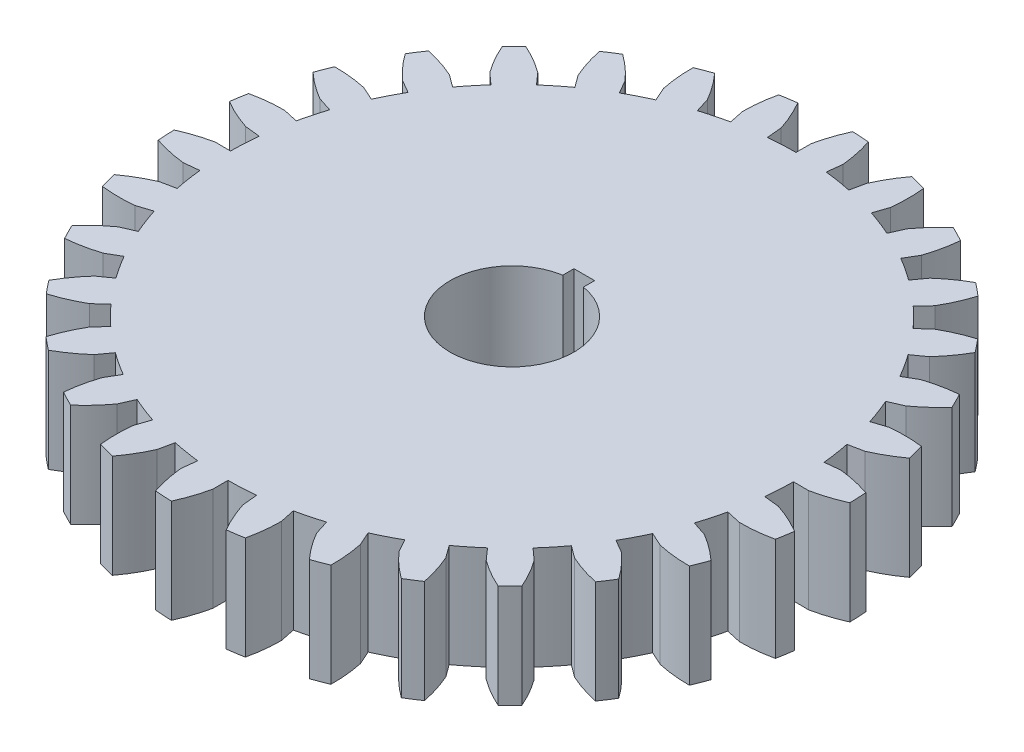
SolidWorks part; units mm, degrees
ref_plane "Front Plane" through (0, 0, 0) normal (0, 0, 1) x (1, 0, 0)
ref_plane "Top Plane" through (0, 0, 0) normal (0, 1, 0) x (1, 0, 0)
ref_plane "Right Plane" through (0, 0, 0) normal (1, 0, 0) x (0, 0, -1)
sketch "Sketch1" plane through (0, 0, 0) normal (0, 1, 0) x (1, 0, 0)
  circle A3 centre (0, 0) radius 13.75
  circle A4 centre (0, 0) radius 16
  circle A5 centre (0, 0) radius 15
  circle A6 centre (0, 0) radius 14
  circle A7 centre (0, 0) radius 14.4889
  dimension "pitch circle" = 30
  dimension "addendum circle" = 32
  dimension "root circle" = 27.5
  dimension "clearance circle" = 28
  dimension "base circle" = 28.9778
sketch "Sketch2" plane through (0, 0, 0) normal (0, 1, 0) x (1, 0, 0)
  line L0 (0, 0) -> (0, 14.4889)
  line L1 (0, 0) -> (7.2444, 12.5477) construction
  line L2 (0, 0) -> (12.5477, 7.2444) construction
  line L3 (0, 0) -> (14.4889, 0) construction
  line L4 (14.4889, 0) -> (14.4889, 22.7591) construction
  line L5 (12.5477, 7.2444) -> (4.9614, 20.3844) construction
  line L6 (7.2444, 12.5477) -> (0.6745, 16.3409) construction
  line L7 (0, 0) -> (3.1187, 14.6722)
  line L8 (0, 0) -> (1.5679, 14.9178) construction
  line L9 (0.8496, 14.9759) -> (0, 0) construction
  circle A0 centre (0, 0) radius 14.4889 construction
  circle A1 centre (0, 0) radius 15 construction
  arc A2 (1.5679, 14.9178) -> (0.1294, 14.9994) centre (0, 0) ccw
  spline S0 degree 3 poles (0, 14.4889) (1.2745, 20.4223) (9.5995, 22.7668) (14.4889, 22.7591) knots 0 0 0 0 1 1 1 1
  spline S1 degree 3 poles (1.6388, 14.3959) (1.0435, 20.4354) (-6.9629, 23.7065) (-11.8218, 24.2518) knots 0 0 0 0 1 1 1 1
  point P11 (0, 0)
  dimension "Involute Control" = 90
  dimension "Base circle quarter circumference" = 22.7591
  dimension "D1" = 15.1727
  dimension "D2" = 7.5864
  dimension "pitch circle" = 12
  dimension "Involute array" = 4
sketch "Sketch3" plane through (0, 0, 0) normal (0, 1, 0) x (1, 0, 0)
  line L0 (1.6388, 14.3959) -> (1.5552, 13.6618)
  line L1 (0, 0) -> (0, 14.4889) construction
  line L3 (0, 13.75) -> (0, 14.4889)
  arc A1 (0.502, 15.9921) -> (0, 14.4889) centre (7.0112, 12.9829) ccw
  circle A2 centre (0, 0) radius 16 construction
  circle A3 centre (0, 0) radius 13.75 construction
  arc A7 (1.6388, 14.3959) -> (1.31, 15.9463) centre (-5.4978, 13.6925) ccw
  arc A8 (1.5552, 13.6618) -> (0, 13.75) centre (0, 0) ccw
  arc A9 (1.31, 15.9463) -> (0.502, 15.9921) centre (0, 0) ccw
  circle A10 centre (0, 0) radius 14.4889 construction
  spline S0 degree 3 poles (1.6388, 14.3959) (1.0435, 20.4354) (-6.9629, 23.7065) (-11.8218, 24.2518) knots 0 0 0 0 1 1 1 1 construction
  spline S1 degree 3 poles (0, 14.4889) (1.2745, 20.4223) (9.5995, 22.7668) (14.4889, 22.7591) knots 0 0 0 0 1 1 1 1 construction
extrude "Boss-Extrude1" add sketch "Sketch3" along normal blind 5
sketch "Sketch5" plane through (0, 0, 0) normal (1, 0, 0) x (0, 0, -1)
  line L0 (0, 0) -> (0, 5.4709) construction
pattern_circular "CirPattern4" count 30 over 360 about axis through (0, 0, 0) along (0, 1, 0) reverse direction yes of bodies 101
sketch "Sketch6" plane through (0, 0, 0) normal (0, 1, 0) x (1, 0, 0)
  circle A0 centre (0, 0) radius 13.75 construction
  circle A1 centre (0, 0) radius 13.75
extrude "Boss-Extrude2" add sketch "Sketch6" along normal up to surface (5 mm away) up to face at (2.2427, 5, 14.5662)
sketch "Sketch7" plane through (0, 5, 0) normal (0, 1, 0) x (1, 0, 0)
  line L1 (-0.5, 3.5) -> (0.5, 3.5)
  line L2 (-0.5, 3.5) -> (-0.5, 2.5)
  line L3 (-0.5, 2.5) -> (0.5, 2.5)
  line L4 (0.5, 3.5) -> (0.5, 2.5)
  line L5 (-0.5, 3.5) -> (0.5, 2.5) construction
  line L6 (-0.5, 2.5) -> (0.5, 3.5) construction
  circle A0 centre (0, 0) radius 3
  point P3 (0, 3)
  dimension "D1" = 6
  dimension "D2" = 1
extrude "Cut-Extrude1" cut sketch "Sketch7" against normal through all contours L2 A0 L4 L3 | L4 A0 L2 L3 | L4 L3 L2 L1 region at (0, 5, -2.7432) region at (0, 5, 0.048)
equation "\"Module\"= 1"
equation "\"Teeth number\"= 30"
equation "\"Pressure angle\"= 15"
equation "\"pitch circle@Sketch1\"= \"Module\" * \"Teeth number\""
equation "\"addendum circle@Sketch1\"= \"pitch circle@Sketch1\" + ( \"Module\" * 2 )"
equation "\"root circle@Sketch1\"= \"pitch circle@Sketch1\" - ( ( \"Module\" * 1.25 ) * 2 )"
equation "\"clearance circle@Sketch1\"= \"pitch circle@Sketch1\" - ( \"Module\" * 2 )"
equation "\"base circle@Sketch1\"= \"pitch circle@Sketch1\" * cos ( \"Pressure angle\" )"
equation "\"D1@Sketch2\"=\"Base circle quarter circumference@Sketch2\"/3*2"
equation "\"D2@Sketch2\"=\"Base circle quarter circumference@Sketch2\"/3"
equation "\"pitch circle@Sketch2\"=360/\"Teeth number\""
equation "\"D1@CirPattern4\"=\"Teeth number\""
equation "\"Base circle quarter circumference@Sketch2\"= \"base circle@Sketch1\" * pi / 4"
